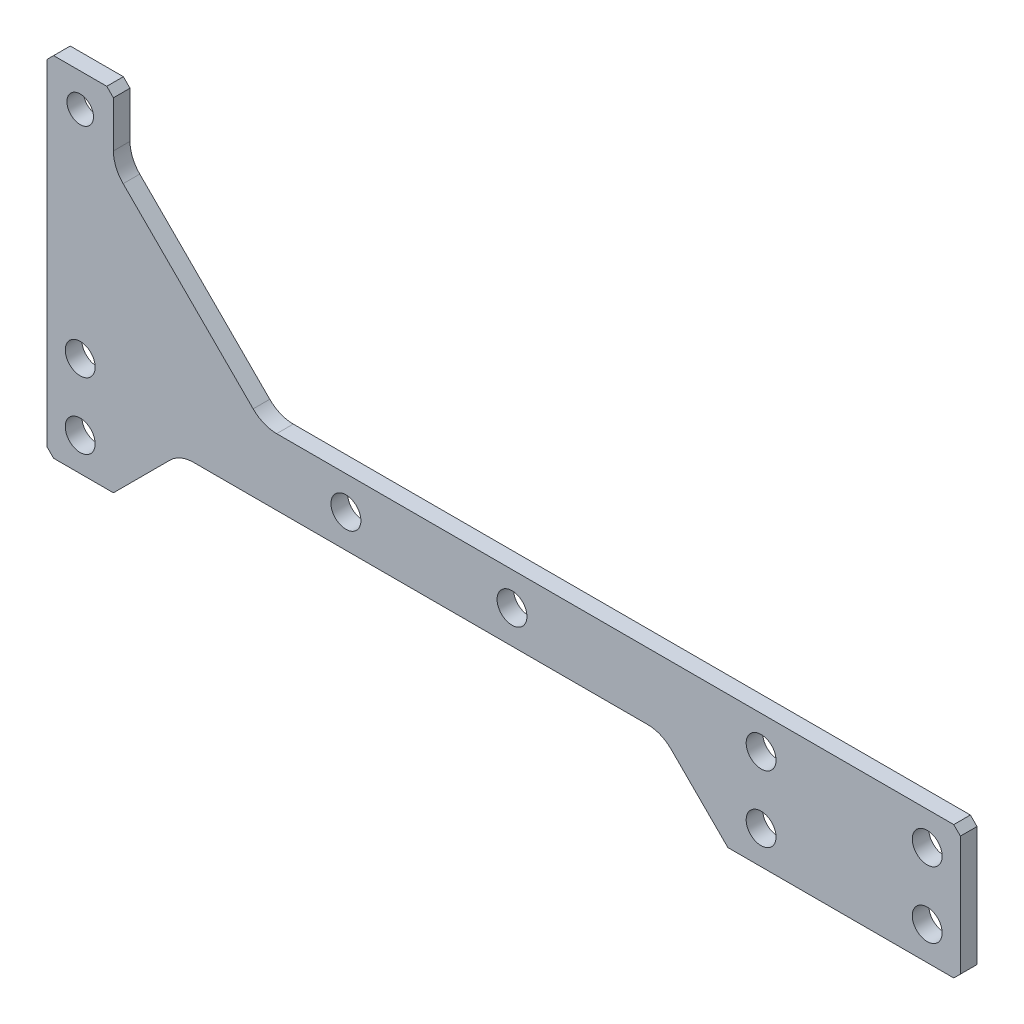
SolidWorks part; units mm, degrees
ref_plane "前视基准面" through (0, 0, 0) normal (0, 0, 1) x (1, 0, 0)
ref_plane "上视基准面" through (0, 0, 0) normal (0, 1, 0) x (1, 0, 0)
ref_plane "右视基准面" through (0, 0, 0) normal (1, 0, 0) x (0, 0, -1)
sketch "草图1" plane through (0, 0, 0) normal (0, 0, 1) x (1, 0, 0)
  line L0 (0, 0) -> (-205, 0) construction
  line L1 (-215, 70) -> (-215, 75)
  line L8 (-215, 75) -> (-195, 75) construction
  line L11 (-10, -10) -> (10, -10)
  line L13 (0, 0) -> (10, -10) construction
  line L14 (-10, -10) -> (0, 0) construction
  line L15 (-195, 30) -> (-195, 70) construction
  line L18 (0, 0) -> (50, 0) construction
  line L22 (40, -10) -> (60, -10)
  line L23 (60, 10) -> (60, -10)
  line L24 (50, 0) -> (60, -10) construction
  line L25 (40, -10) -> (50, 0) construction
  line L26 (10, -10) -> (40, -10)
  line L27 (60, 10) -> (60, 30)
  line L28 (60, 30) -> (-150, 30)
  line L29 (-10, -10) -> (-10, 10)
  line L30 (-10, 10) -> (-10, -10) construction
  line L31 (60, 10) -> (-10, 10) construction
  line L32 (-10, 10) -> (-195, 10)
  line L33 (-215, 10) -> (-215, 70)
  line L34 (-215, 75) -> (-215, 95)
  line L35 (-205, 10) -> (-205, 20) construction
  line L36 (0, 0) -> (0, 20) construction
  line L39 (-215, 95) -> (-195, 95)
  line L40 (-195, -10) -> (-215, -10)
  line L41 (-195, -10) -> (-195, 10)
  line L43 (-215, -10) -> (-215, 10)
  line L44 (-195, -10) -> (-215, 10) construction
  line L45 (-195, 10) -> (-215, -10) construction
  line L47 (-205, 95) -> (-205, 75) construction
  line L50 (-150, 30) -> (-195, 75)
  line L51 (-195, 95) -> (-195, 75)
  circle A1 centre (0, 0) radius 4.5
  circle A2 centre (50, 0) radius 4.5
  circle A3 centre (-205, 20) radius 4.5
  circle A4 centre (0, 20) radius 4.5
  circle A5 centre (-205, 0) radius 4.5
  circle A6 centre (-205, 85) radius 4
  point P92 (-205, 90)
  dimension "D1" = 60
  dimension "D4" = 20
  dimension "D6" = 5
  dimension "D2" = 20
  dimension "D12" = 10
  dimension "D3" = 40
  dimension "D5" = 205
  dimension "D7" = 20
  dimension "D8" = 20
  dimension "D9" = 20
  dimension "D10" = 30
  dimension "D11" = 20
extrude "凸台-拉伸1" add sketch "草图1" along normal blind 5
chamfer "倒角2" distance 20 angle 45 1 edges at (-10, 10, 2.5)
chamfer "倒角3" distance 20 angle 45 1 edges at (-195, 10, 2.5)
sketch "草图2" plane through (0, 0, 5) normal (0, 0, 1) x (1, 0, 0)
  line L0 (-205, 20) -> (-125, 19.986) construction
  line L1 (-125, 19.986) -> (-75, 19.986) construction
  circle A0 centre (-125, 19.986) radius 4.5
  circle A1 centre (-75, 19.986) radius 4.5
extrude "切除-拉伸1" cut sketch "草图2" against normal up to surface (5 mm away) up to face at (-200.5, 0, 0)
fillet "圆角1" radius 10 4 edges at (-195, 75, 2.5) (-150, 30, 2.5) (-175, 10, 2.5) (-30, 10, 2.5)
chamfer "倒角4" distance 2 angle 45 5 edges at (60, -10, 2.5) (60, 30, 2.5) (-215, -10, 2.5) (-195, 95, 2.5) (-215, 95, 2.5)
sketch "草图3" plane through (0, 0, 5) normal (0, 0, 1) x (1, 0, 0)
  line L0 (50, 0) -> (50, 20) construction
  circle A0 centre (50, 20) radius 4.5
extrude "切除-拉伸2" cut sketch "草图3" against normal blind 10
